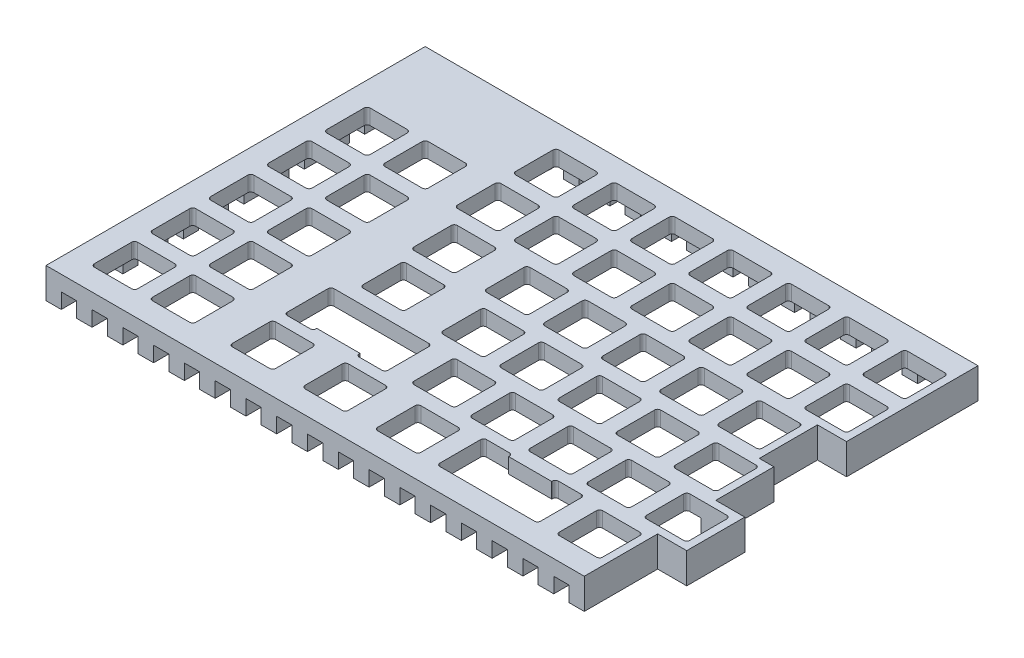
SolidWorks part; units mm, degrees
ref_plane "Front Plane" through (0, 0, 0) normal (0, 0, 1) x (1, 0, 0)
ref_plane "Top Plane" through (0, 0, 0) normal (0, 1, 0) x (1, 0, 0)
ref_plane "Right Plane" through (0, 0, 0) normal (1, 0, 0) x (0, 0, -1)
sketch "Sketch1" plane through (0, 0, 0) normal (0, 1, 0) x (1, 0, 0)
  line L0 (0, 0) -> (0, 124.3)
  line L1 (0, 124.3) -> (181.2125, 124.3)
  line L2 (181.2125, 124.3) -> (181.2125, 81.2)
  line L3 (181.2125, 81.2) -> (171.6875, 81.2)
  line L4 (171.6875, 81.2) -> (171.6875, 62.15)
  line L5 (171.6875, 62.15) -> (176.45, 62.15)
  line L6 (176.45, 62.15) -> (176.45, 43.1)
  line L7 (176.45, 43.1) -> (185.975, 43.1)
  line L8 (185.975, 43.1) -> (185.975, 24.05)
  line L9 (185.975, 24.05) -> (176.45, 24.05)
  line L10 (176.45, 24.05) -> (176.45, 0)
  line L11 (176.45, 0) -> (0, 0)
  dimension "D2" = 181.2125
  dimension "D3" = 43.1
  dimension "D4" = 4.7625
  dimension "D5" = 9.525
  dimension "D6" = 19.05
  dimension "D1" = 24.05
extrude "Plate Frame" add sketch "Sketch1" along normal blind 5
sketch "Sketch4" plane through (0, 5, 0) normal (0, 1, 0) x (1, 0, 0)
  line L0 (14.525, 90.725) -> (33.575, 90.725) construction
  line L1 (33.575, 90.725) -> (33.575, 71.675) construction
  line L2 (33.575, 71.675) -> (33.575, 52.625) construction
  line L3 (33.575, 52.625) -> (33.575, 33.575) construction
  line L4 (33.575, 33.575) -> (33.575, 14.525) construction
  line L5 (33.575, 14.525) -> (14.525, 14.525) construction
  line L6 (14.525, 14.525) -> (14.525, 33.575) construction
  line L7 (14.525, 33.575) -> (14.525, 52.625) construction
  line L8 (14.525, 52.625) -> (14.525, 71.675) construction
  line L9 (14.525, 71.675) -> (14.525, 90.725) construction
  line L10 (14.525, 71.675) -> (33.575, 71.675) construction
  line L11 (14.525, 52.625) -> (33.575, 52.625) construction
  line L12 (14.525, 33.575) -> (33.575, 33.575) construction
  line L13 (57.3875, 109.775) -> (57.3875, 90.725) construction
  line L14 (57.3875, 90.725) -> (76.4375, 90.725) construction
  line L15 (76.4375, 90.725) -> (76.4375, 109.775) construction
  line L16 (76.4375, 109.775) -> (95.4875, 109.775) construction
  line L17 (95.4875, 109.775) -> (114.5375, 109.775) construction
  line L18 (114.5375, 109.775) -> (133.5875, 109.775) construction
  line L19 (133.5875, 109.775) -> (152.6375, 109.775) construction
  line L20 (152.6375, 109.775) -> (171.6875, 109.775) construction
  line L21 (171.6875, 109.775) -> (171.6875, 90.725) construction
  line L22 (171.6875, 90.725) -> (152.6375, 90.725) construction
  line L23 (152.6375, 90.725) -> (133.5875, 90.725) construction
  line L24 (133.5875, 90.725) -> (114.5375, 90.725) construction
  line L25 (114.5375, 90.725) -> (95.4875, 90.725) construction
  line L26 (95.4875, 90.725) -> (76.4375, 90.725) construction
  line L27 (57.3875, 109.775) -> (76.4375, 109.775) construction
  line L28 (95.4875, 109.775) -> (95.4875, 90.725) construction
  line L29 (114.5375, 90.725) -> (114.5375, 109.775) construction
  line L30 (133.5875, 109.775) -> (133.5875, 90.725) construction
  line L31 (152.6375, 90.725) -> (152.6375, 109.775) construction
  line L32 (62.15, 71.675) -> (85.9625, 71.675) construction
  line L33 (85.9625, 71.675) -> (105.0125, 71.675) construction
  line L34 (105.0125, 71.675) -> (124.0625, 71.675) construction
  line L35 (124.0625, 71.675) -> (143.1125, 71.675) construction
  line L36 (143.1125, 71.675) -> (162.1625, 71.675) construction
  line L37 (90.725, 52.625) -> (109.775, 52.625) construction
  line L38 (109.775, 52.625) -> (128.825, 52.625) construction
  line L39 (128.825, 52.625) -> (147.875, 52.625) construction
  line L40 (147.875, 52.625) -> (166.925, 52.625) construction
  line L41 (100.25, 33.575) -> (119.3, 33.575) construction
  line L42 (119.3, 33.575) -> (138.35, 33.575) construction
  line L43 (138.35, 33.575) -> (157.4, 33.575) construction
  line L44 (157.4, 33.575) -> (176.45, 33.575) construction
  line L45 (171.6875, 71.675) -> (162.1625, 71.675) construction
  line L46 (171.6875, 62.15) -> (171.6875, 81.2) construction
  line L49 (59.7687, 14.525) -> (83.5812, 14.525) construction
  line L50 (83.5812, 14.525) -> (107.3937, 14.525) construction
  line L51 (64.5312, 52.625) -> (90.725, 52.625) construction
  line L52 (107.3937, 14.525) -> (166.925, 14.525) construction
  point P0 (14.525, 14.525)
  point P1 (33.575, 14.525)
  point P2 (33.575, 33.575)
  point P3 (14.525, 33.575)
  point P4 (14.525, 52.625)
  point P5 (33.575, 52.625)
  point P6 (33.575, 71.675)
  point P7 (14.525, 71.675)
  point P8 (14.525, 90.725)
  point P9 (33.575, 90.725)
  point P12 (57.3875, 109.775)
  point P21 (57.3875, 90.725)
  point P22 (76.4375, 90.725)
  point P23 (76.4375, 109.775)
  point P24 (95.4875, 109.775)
  point P25 (95.4875, 90.725)
  point P26 (114.5375, 90.725)
  point P27 (114.5375, 109.775)
  point P28 (133.5875, 109.775)
  point P29 (133.5875, 90.725)
  point P30 (152.6375, 90.725)
  point P31 (152.6375, 109.775)
  point P32 (171.6875, 109.775)
  point P33 (171.6875, 90.725)
  point P44 (85.9625, 71.675)
  point P49 (62.15, 71.675)
  point P50 (105.0125, 71.675)
  point P51 (124.0625, 71.675)
  point P52 (143.1125, 71.675)
  point P53 (162.1625, 71.675)
  point P54 (90.725, 52.625)
  point P55 (109.775, 52.625)
  point P56 (128.825, 52.625)
  point P57 (147.875, 52.625)
  point P58 (166.925, 52.625)
  point P59 (100.25, 33.575)
  point P60 (119.3, 33.575)
  point P61 (138.35, 33.575)
  point P62 (157.4, 33.575)
  point P63 (176.45, 33.575)
  point P81 (83.5812, 14.525)
  point P82 (107.3937, 14.525)
  point P83 (64.5312, 52.625)
  point P90 (166.925, 14.525)
  point P94 (59.7687, 14.525)
  dimension "D1" = 19.05
  dimension "D2" = 9.525
  dimension "D3" = 23.8125
  dimension "D4" = 23.8125
  dimension "D6" = 9.525
  dimension "D5" = 4.7625
  dimension "D7" = 9.525
  dimension "D8" = 23.8125
  dimension "D9" = 26.1938
  dimension "D10" = 26.1938
  dimension "D11" = 59.5312
sketch "Sketch2" plane through (0, 5, 0) normal (0, 1, 0) x (1, 0, 0)
  line L0 (7.425, 8.425) -> (7.425, 20.625)
  line L1 (8.425, 21.625) -> (20.625, 21.625)
  line L2 (21.625, 20.625) -> (21.625, 8.425)
  line L3 (20.625, 7.425) -> (8.425, 7.425)
  line L4 (8.425, 21.625) -> (20.625, 7.425) construction
  arc A0 (7.425, 20.625) -> (8.425, 21.625) centre (8.425, 20.625) cw
  arc A1 (20.625, 21.625) -> (21.625, 20.625) centre (20.625, 20.625) cw
  arc A2 (21.625, 8.425) -> (20.625, 7.425) centre (20.625, 8.425) cw
  arc A3 (8.425, 7.425) -> (7.425, 8.425) centre (8.425, 8.425) cw
  point P12 (14.525, 14.525)
  dimension "D3" = 1
  dimension "D1" = 14.2
extrude "1U" cut sketch "Sketch2" against normal through all
pattern_sketch "Sketch-Pattern1" of "1U" driven by "Sketch4"
sketch "Sketch5" plane through (0, 5, 0) normal (0, 1, 0) x (1, 0, 0)
  line L0 (107.3937, 14.525) -> (166.925, 14.525) construction
  line L1 (69.2937, 33.575) -> (100.25, 33.575) construction
  point P0 (69.2937, 33.575)
  point P1 (137.1594, 14.525)
  point P4 (137.1594, 14.525)
  dimension "D1" = 30.9563
sketch "Sketch6" plane through (0, 5, 0) normal (0, 1, 0) x (1, 0, 0)
  line L0 (52.7937, 26.325) -> (52.7937, 39.625)
  line L1 (53.7937, 40.625) -> (84.7937, 40.625)
  line L2 (85.7937, 39.625) -> (85.7937, 26.325)
  line L3 (84.7937, 25.325) -> (77.3437, 25.325)
  line L5 (61.2437, 25.325) -> (53.7937, 25.325)
  line L6 (62.2437, 26.325) -> (62.2437, 26.525)
  line L7 (62.2437, 26.525) -> (76.3437, 26.525)
  line L8 (76.3437, 26.525) -> (76.3437, 26.325)
  line L9 (62.2437, 26.525) -> (76.3437, 40.625) construction
  arc A0 (52.7937, 39.625) -> (53.7937, 40.625) centre (53.7937, 39.625) cw
  arc A1 (84.7937, 40.625) -> (85.7937, 39.625) centre (84.7937, 39.625) cw
  arc A2 (85.7937, 26.325) -> (84.7937, 25.325) centre (84.7937, 26.325) cw
  arc A3 (77.3437, 25.325) -> (76.3437, 26.325) centre (77.3437, 26.325) cw
  arc A4 (62.2437, 26.325) -> (61.2437, 25.325) centre (61.2437, 26.325) cw
  arc A5 (53.7937, 25.325) -> (52.7937, 26.325) centre (53.7937, 26.325) cw
  point P23 (69.2937, 33.575)
  dimension "D1" = 1
  dimension "D2" = 14.1
  dimension "D3" = 33
  dimension "D4" = 14.1
  dimension "D5" = 15.3
sketch "Sketch7" plane through (0, 5, 0) normal (0, 1, 0) x (1, 0, 0)
  line L10 (121.6594, 7.475) -> (152.6594, 7.475)
  line L11 (153.6594, 8.475) -> (153.6594, 21.775)
  line L12 (152.6594, 22.775) -> (145.2094, 22.775)
  line L13 (144.2094, 21.775) -> (144.2094, 21.575)
  line L14 (144.2094, 21.575) -> (130.1094, 21.575)
  line L15 (130.1094, 21.575) -> (130.1094, 21.775)
  line L16 (129.1094, 22.775) -> (121.6594, 22.775)
  line L17 (120.6594, 21.775) -> (120.6594, 8.475)
  line L18 (144.2094, 21.575) -> (130.1094, 7.475) construction
  arc A6 (152.6594, 7.475) -> (153.6594, 8.475) centre (152.6594, 8.475) ccw
  arc A7 (153.6594, 21.775) -> (152.6594, 22.775) centre (152.6594, 21.775) ccw
  arc A8 (145.2094, 22.775) -> (144.2094, 21.775) centre (145.2094, 21.775) ccw
  arc A10 (121.6594, 22.775) -> (120.6594, 21.775) centre (121.6594, 21.775) ccw
  arc A11 (120.6594, 8.475) -> (121.6594, 7.475) centre (121.6594, 8.475) ccw
  arc A12 (129.1094, 22.775) -> (130.1094, 21.775) centre (129.1094, 21.775) cw
  point P43 (137.1594, 14.525)
  dimension "D6" = 1
  dimension "D7" = 14.1
  dimension "D8" = 15.3
  dimension "D9" = 33
  dimension "D10" = 14.1
extrude "Cut-Extrude1" cut sketch "Sketch6" against normal through all
extrude "Cut-Extrude2" cut sketch "Sketch7" against normal through all
sketch "Sketch8" plane through (0, 0, 0) normal (0, -1, 0) x (1, 0, 0)
  line L0 (176.45, 0) -> (0, 0)
  line L1 (0, 0) -> (0, -124.3)
  line L2 (0, -124.3) -> (181.2125, -124.3)
  line L3 (181.2125, -124.3) -> (181.2125, -81.2)
  line L4 (181.2125, -81.2) -> (171.6875, -81.2)
  line L5 (171.6875, -81.2) -> (171.6875, -62.15)
  line L6 (171.6875, -62.15) -> (176.45, -62.15)
  line L7 (176.45, -62.15) -> (176.45, -43.1)
  line L8 (176.45, -43.1) -> (185.975, -43.1)
  line L9 (185.975, -43.1) -> (185.975, -24.05)
  line L10 (185.975, -24.05) -> (176.45, -24.05)
  line L11 (176.45, -24.05) -> (176.45, 0)
  line L12 (5, -5) -> (174.025, -5)
  line L13 (174.025, -5) -> (174.025, -26.475)
  line L14 (170.35, -26.475) -> (182.55, -26.475) construction
  line L15 (174.025, -26.475) -> (183.55, -26.475)
  line L16 (183.55, -26.475) -> (183.55, -40.675)
  line L17 (183.55, -40.675) -> (174.025, -40.675)
  line L18 (182.55, -40.675) -> (170.35, -40.675) construction
  line L19 (174.025, -40.675) -> (174.025, -59.725)
  line L20 (174.025, -59.725) -> (169.2625, -59.725)
  line L21 (173.025, -59.725) -> (160.825, -59.725) construction
  line L22 (169.2625, -59.725) -> (169.2625, -83.625)
  line L23 (165.5875, -83.625) -> (177.7875, -83.625) construction
  line L24 (169.2625, -83.625) -> (178.7875, -83.625)
  line L25 (178.7875, -83.625) -> (178.7875, -119.3)
  line L26 (178.7875, -119.3) -> (5, -119.3)
  line L27 (5, -119.3) -> (5, -5)
  line L28 (174.025, -8.425) -> (174.025, -20.625) construction
  line L29 (178.7875, -84.625) -> (178.7875, -96.825) construction
  line L30 (183.55, -27.475) -> (183.55, -39.675) construction
  line L31 (174.025, -46.525) -> (174.025, -58.725) construction
  line L32 (169.2625, -65.575) -> (169.2625, -77.775) construction
  dimension "D1" = 5
  dimension "D2" = 5
  dimension "D3" = 5
extrude "Boss-Extrude1" add sketch "Sketch8" along normal blind 5
sketch "Sketch9" plane through (0, 0, 0) normal (1, 0, 0) x (0, 0, -1)
  line L0 (124.3, 0) -> (0, 0) construction
  line L3 (124.3, 5) -> (124.3, -5) construction
  line L4 (0, 5) -> (0, -5) construction
  line L36 (0, -5) -> (124.3, -5) construction
  line L45 (119.3, 0) -> (114.3, 0)
  line L46 (119.3, 0) -> (119.3, -5)
  line L47 (119.3, -5) -> (114.3, -5)
  line L48 (114.3, 0) -> (114.3, -5)
  line L49 (109.39, 0) -> (104.39, 0)
  line L50 (109.39, 0) -> (109.39, -5)
  line L51 (109.39, -5) -> (104.39, -5)
  line L52 (104.39, 0) -> (104.39, -5)
  line L53 (99.48, 0) -> (94.48, 0)
  line L54 (99.48, 0) -> (99.48, -5)
  line L55 (99.48, -5) -> (94.48, -5)
  line L56 (94.48, 0) -> (94.48, -5)
  line L57 (89.57, 0) -> (84.57, 0)
  line L58 (89.57, 0) -> (89.57, -5)
  line L59 (89.57, -5) -> (84.57, -5)
  line L60 (84.57, 0) -> (84.57, -5)
  line L61 (79.66, 0) -> (74.66, 0)
  line L62 (79.66, 0) -> (79.66, -5)
  line L63 (79.66, -5) -> (74.66, -5)
  line L64 (74.66, 0) -> (74.66, -5)
  line L65 (69.75, 0) -> (64.75, 0)
  line L66 (69.75, 0) -> (69.75, -5)
  line L67 (69.75, -5) -> (64.75, -5)
  line L68 (64.75, 0) -> (64.75, -5)
  line L69 (59.84, 0) -> (54.84, 0)
  line L70 (59.84, 0) -> (59.84, -5)
  line L71 (59.84, -5) -> (54.84, -5)
  line L72 (54.84, 0) -> (54.84, -5)
  line L73 (49.93, 0) -> (44.93, 0)
  line L74 (49.93, 0) -> (49.93, -5)
  line L75 (49.93, -5) -> (44.93, -5)
  line L76 (44.93, 0) -> (44.93, -5)
  line L77 (40.02, 0) -> (35.02, 0)
  line L78 (40.02, 0) -> (40.02, -5)
  line L79 (40.02, -5) -> (35.02, -5)
  line L80 (35.02, 0) -> (35.02, -5)
  line L81 (30.11, 0) -> (25.11, 0)
  line L82 (30.11, 0) -> (30.11, -5)
  line L83 (30.11, -5) -> (25.11, -5)
  line L84 (25.11, 0) -> (25.11, -5)
  line L85 (20.2, 0) -> (15.2, 0)
  line L86 (20.2, 0) -> (20.2, -5)
  line L87 (20.2, -5) -> (15.2, -5)
  line L88 (15.2, 0) -> (15.2, -5)
  line L90 (5, 0) -> (10, 0)
  line L91 (5, 0) -> (5, -5)
  line L92 (5, -5) -> (10, -5)
  line L93 (10, 0) -> (10, -5)
  dimension "D1" = 5
  dimension "D2" = 5
  dimension "D4" = 4.91
  dimension "D5" = 5
  dimension "D6" = 5
  dimension "D3" = 11
extrude "Cut-Extrude5" cut sketch "Sketch9" along normal up to next
sketch "Sketch10" plane through (0, 0, 0) normal (0, 0, 1) x (1, 0, 0)
  line L0 (0, 0) -> (176.45, 0) construction
  line L1 (176.45, -5) -> (0, -5) construction
  line L2 (5, 0) -> (10, 0)
  line L3 (5, 0) -> (5, -5)
  line L4 (5, -5) -> (10, -5)
  line L5 (10, 0) -> (10, -5)
  line L6 (0, 5) -> (0, -5) construction
  line L63 (15.09, 0) -> (20.09, 0)
  line L64 (15.09, 0) -> (15.09, -5)
  line L69 (176.45, 5) -> (176.45, -5) construction
  line L70 (15.09, -5) -> (20.09, -5)
  line L71 (20.09, 0) -> (20.09, -5)
  line L72 (25.18, 0) -> (30.18, 0)
  line L73 (25.18, 0) -> (25.18, -5)
  line L74 (25.18, -5) -> (30.18, -5)
  line L75 (30.18, 0) -> (30.18, -5)
  line L76 (35.27, 0) -> (40.27, 0)
  line L77 (35.27, 0) -> (35.27, -5)
  line L78 (35.27, -5) -> (40.27, -5)
  line L79 (40.27, 0) -> (40.27, -5)
  line L80 (45.36, 0) -> (50.36, 0)
  line L81 (45.36, 0) -> (45.36, -5)
  line L82 (45.36, -5) -> (50.36, -5)
  line L83 (50.36, 0) -> (50.36, -5)
  line L84 (55.45, 0) -> (60.45, 0)
  line L85 (55.45, 0) -> (55.45, -5)
  line L86 (55.45, -5) -> (60.45, -5)
  line L87 (60.45, 0) -> (60.45, -5)
  line L88 (65.54, 0) -> (70.54, 0)
  line L89 (65.54, 0) -> (65.54, -5)
  line L90 (65.54, -5) -> (70.54, -5)
  line L91 (70.54, 0) -> (70.54, -5)
  line L92 (75.63, 0) -> (80.63, 0)
  line L93 (75.63, 0) -> (75.63, -5)
  line L94 (75.63, -5) -> (80.63, -5)
  line L95 (80.63, 0) -> (80.63, -5)
  line L96 (85.72, 0) -> (90.72, 0)
  line L97 (85.72, 0) -> (85.72, -5)
  line L98 (85.72, -5) -> (90.72, -5)
  line L99 (90.72, 0) -> (90.72, -5)
  line L100 (95.81, 0) -> (100.81, 0)
  line L101 (95.81, 0) -> (95.81, -5)
  line L102 (95.81, -5) -> (100.81, -5)
  line L103 (100.81, 0) -> (100.81, -5)
  line L104 (105.9, 0) -> (110.9, 0)
  line L105 (105.9, 0) -> (105.9, -5)
  line L106 (105.9, -5) -> (110.9, -5)
  line L107 (110.9, 0) -> (110.9, -5)
  line L108 (115.99, 0) -> (120.99, 0)
  line L109 (115.99, 0) -> (115.99, -5)
  line L110 (115.99, -5) -> (120.99, -5)
  line L111 (120.99, 0) -> (120.99, -5)
  line L112 (126.08, 0) -> (131.08, 0)
  line L113 (126.08, 0) -> (126.08, -5)
  line L114 (126.08, -5) -> (131.08, -5)
  line L115 (131.08, 0) -> (131.08, -5)
  line L116 (136.17, 0) -> (141.17, 0)
  line L117 (136.17, 0) -> (136.17, -5)
  line L118 (136.17, -5) -> (141.17, -5)
  line L119 (141.17, 0) -> (141.17, -5)
  line L120 (146.26, 0) -> (151.26, 0)
  line L121 (146.26, 0) -> (146.26, -5)
  line L122 (146.26, -5) -> (151.26, -5)
  line L123 (151.26, 0) -> (151.26, -5)
  line L124 (156.35, 0) -> (161.35, 0)
  line L125 (156.35, 0) -> (156.35, -5)
  line L126 (156.35, -5) -> (161.35, -5)
  line L127 (161.35, 0) -> (161.35, -5)
  line L128 (176.45, 5) -> (176.45, -5) construction
  line L129 (166.45, 0) -> (171.45, 0)
  line L130 (166.45, 0) -> (166.45, -5)
  line L131 (166.45, -5) -> (171.45, -5)
  line L132 (171.45, 0) -> (171.45, -5)
  dimension "D1" = 5
  dimension "D2" = 5
  dimension "D4" = 5
  dimension "D5" = 5
  dimension "D6" = 5.09
  dimension "D3" = 16
extrude "Cut-Extrude6" cut sketch "Sketch10" against normal through all
equation "\"D2@Sketch4\"=19.05/2"
equation "\"D3@Sketch4\"=19.05/2 + (19.05*1.5)/2"
equation "\"D4@Sketch4\"=19.05/2 + 19.05*.25 + 19.05/2"
equation "\"D6@Sketch4\"=19.05/2"
equation "\"D5@Sketch4\"=19.05/4"
equation "\"D7@Sketch4\"=19.05/2"
equation "\"D5@Sketch1\"=19.05/2"
equation "\"D4@Sketch1\"=19.05/4"
equation "\"D8@Sketch4\"=19.05*1.25"
equation "\"D9@Sketch4\"=19.05/2 + 19.05*1.75/2"
equation "\"D10@Sketch4\"=19.05/2 + 19.05*.25 + 19.05*1.25/2"
equation "\"D11@Sketch4\"=19.05*1.25/2 + 19.05*2 + 19.05/2"
equation "\"D1@Sketch5\"=19.05*2.25/2 + 19.05/2"
equation "\"D3@Sketch1\"=19.05*2 + 5"
equation "\"D1@Sketch1\"=19.05 + 5"
equation "\"D2@Sketch1\"=9.25*19.05 + 5"
